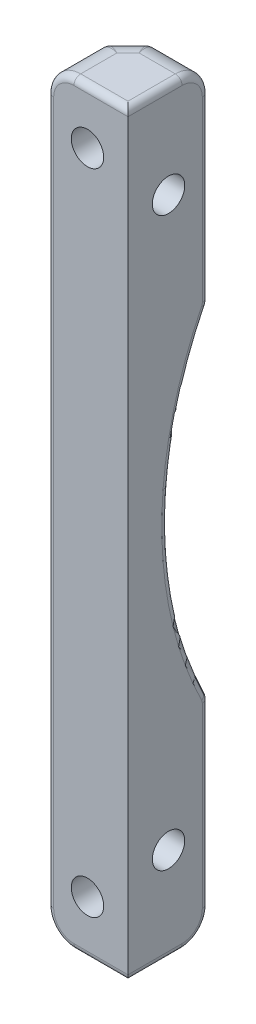
SolidWorks part; units mm, degrees
ref_plane "Front Plane" through (0, 0, 0) normal (0, 0, 1) x (1, 0, 0)
ref_plane "Top Plane" through (0, 0, 0) normal (0, 1, 0) x (1, 0, 0)
ref_plane "Right Plane" through (0, 0, 0) normal (1, 0, 0) x (0, 0, -1)
sketch "Sketch1" plane through (0, 0, 0) normal (1, 0, 0) x (0, 0, -1)
  line L0 (0, 44.45) -> (0, -44.45)
  line L1 (0, -44.45) -> (9.525, -44.45)
  line L2 (9.525, -44.45) -> (9.525, -20.0176)
  line L3 (0, 44.45) -> (9.525, 44.45)
  line L4 (9.525, 44.45) -> (9.525, 20.0176)
  arc A0 (9.525, 20.0176) -> (9.525, -20.0176) centre (49.2125, 0) ccw
  point P8 (0, 0)
  point P9 (13.3757, 39.1886)
  point P10 (13.7159, -34.925)
  point P11 (4.7625, 0)
  point P12 (-67.7998, 68.0307)
  dimension "D1" = 88.9
  dimension "D4" = 4.7625
  dimension "D2" = 44.45
  dimension "D3" = 9.525
extrude "Boss-Extrude1" add sketch "Sketch1" along normal mid plane 9.525
sketch "Sketch3" plane through (0, 0, 0) normal (0, 0, 1) x (1, 0, 0)
  line L0 (0, -38.1) -> (0, 38.1) construction
  circle A0 centre (0, 38.1) radius 1.905
  circle A1 centre (0, -38.1) radius 1.905
  point P4 (0, 0)
  dimension "D1" = 3.81
  dimension "D2" = 76.2
extrude "Cut-Extrude1" cut sketch "Sketch3" against normal through all
sketch "Sketch4" plane through (4.7625, 0, 0) normal (1, 0, 0) x (0, 0, -1)
  line L0 (4.7625, 33.3375) -> (4.7625, -33.3375) construction
  line L1 (0, 44.45) -> (0, -44.45) construction
  circle A0 centre (4.7625, -33.3375) radius 1.905
  circle A1 centre (4.7625, 33.3375) radius 1.905
  point P4 (4.7625, 0)
  dimension "D1" = 3.81
  dimension "D2" = 66.675
  dimension "D3" = 4.7625
extrude "Cut-Extrude2" cut sketch "Sketch4" against normal through all
chamfer "Chamfer1" distance 3.175 angle 45 3 edges at (-4.7625, 32.2338, -9.525) (-4.7625, -32.2338, -9.525) (-4.7625, 0, -4.7625)
fillet "Fillet3" radius 3.175 6 edges at (-4.7625, -44.45, -3.175) (1.5875, -44.45, -9.525) (-3.175, -44.45, -7.9375) (-4.7625, 44.45, -3.175) (-3.175, 44.45, -7.9375) (1.5875, 44.45, -9.525)
fillet "Fillet2" radius 1.5875 4 edges at (1.5875, 20.0176, -9.525) (1.5875, -20.0176, -9.525)
fillet "Fillet1" radius 0.7937 36 edges at (4.7625, -30.8334, -9.525) (4.7625, 30.8334, -9.525) (4.7625, 0, -4.7625) (-4.7625, 0, 0) (4.7625, -20.0308, -9.4834) (4.7625, 20.0308, -9.4834) (-4.7625, -26.6498, -6.35) (-4.7625, -20.8938, -6.3435) (-1.5875, -28.7194, -9.525) (-1.5884, -20.3378, -9.5241) (-1.5875, 0, -4.7625) (-1.5884, 20.3378, -9.5241) (-4.7625, 26.6498, -6.35) (-4.7625, 20.6436, -6.2868) (-1.5875, 40.214, -9.525) (-1.5875, -40.214, -9.525) (-4.7625, -37.8328, -6.35) (-4.7625, 0, -1.5875) (-1.5875, 28.7194, -9.525) (-4.7625, 37.8328, -6.35) (-1.2023, 43.5201, -8.5951) (-1.2023, -43.5201, -8.5951) (-3.8326, -43.5201, -5.9648) (-3.8326, 43.5201, -5.9648) (4.7625, -44.45, -3.175) (4.7625, -43.5201, -8.5951) (4.7625, 44.45, -3.175) (4.7625, 43.5201, -8.5951) (1.5875, -44.45, 0) (-3.8326, -43.5201, 0) (1.5875, 44.45, 0) (-3.8326, 43.5201, 0)
